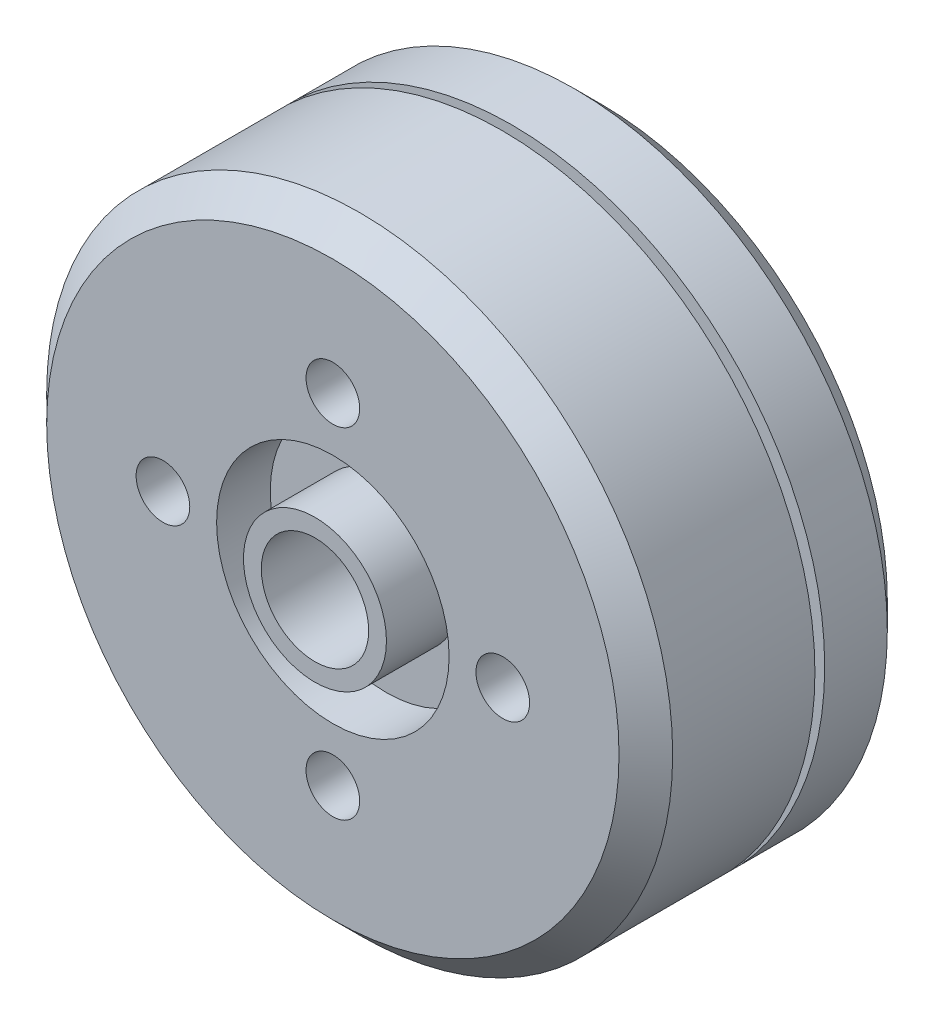
SolidWorks part; units mm, degrees
ref_plane "前视基准面" through (0, 0, 0) normal (0, 0, 1) x (1, 0, 0)
ref_plane "上视基准面" through (0, 0, 0) normal (0, 1, 0) x (1, 0, 0)
ref_plane "右视基准面" through (0, 0, 0) normal (1, 0, 0) x (0, 0, -1)
sketch "草图1" plane through (0, 0, 0) normal (0, 0, 1) x (1, 0, 0)
  circle A0 centre (0, 0) radius 17.5
extrude "凸台-拉伸1" add sketch "草图1" along normal blind 15
sketch "草图2" plane through (0, 0, 0) normal (0, 0, -1) x (-1, 0, 0)
  circle A0 centre (0, -8) radius 1.5
  circle A1 centre (-8, 0) radius 1.5
  circle A2 centre (0, 8) radius 1.5
  circle A3 centre (8, 0) radius 1.5
  point P12 (0, 0)
  dimension "D1" = 4
extrude "切除-拉伸1" cut sketch "草图2" against normal blind 5
sketch "草图3" plane through (0, 0, 0) normal (0, 1, 0) x (1, 0, 0)
  line L0 (17.9693, -5) -> (17.9693, -5.5469)
  line L1 (17.9693, -5) -> (13.2844, -5)
  line L3 (13.2844, -5.0469) -> (13.2844, -5.5469)
  line L4 (13.2844, -5.5469) -> (17.9693, -5.5469)
  line L11 (13.2844, -5) -> (13.2844, -5.0469)
  line L12 (0, 0) -> (0, -15)
  line L13 (-17.5, -15) -> (17.5, -15) construction
revolve "切除-旋转1" cut sketch "草图3" angle 360 about L12
sketch "草图4" plane through (0, 0, 0) normal (0, 0, -1) x (-1, 0, 0)
  circle A0 centre (0, 0) radius 3
extrude "切除-拉伸2" cut sketch "草图4" against normal blind 20
sketch "草图5" plane through (0, 0, 15) normal (0, 0, 1) x (1, 0, 0)
  circle A0 centre (0, -9.5) radius 1.5
  circle A1 centre (-9.5, 0) radius 1.5
  circle A2 centre (0, 9.5) radius 1.5
  circle A3 centre (9.5, 0) radius 1.5
  point P12 (0, 0)
  dimension "D1" = 4
extrude "切除-拉伸3" cut sketch "草图5" against normal blind 6
chamfer "倒角1" distance 1.5 angle 45 2 edges at (17.5, 0, 15) (17.5, 0, 0)
sketch "草图6" plane through (0, 0, 15) normal (0, 0, 1) x (1, 0, 0)
  circle A0 centre (0, 0) radius 6.5
  circle A1 centre (0, 0) radius 3.9966
extrude "切除-拉伸4" cut sketch "草图6" against normal blind 3
sketch "草图7" plane through (0, 0, 15) normal (0, 0, 1) x (1, 0, 0)
  circle A0 centre (0, 0) radius 3
  circle A1 centre (0, 0) radius 3.9966
extrude "凸台-拉伸2" add sketch "草图7" along normal blind 1
